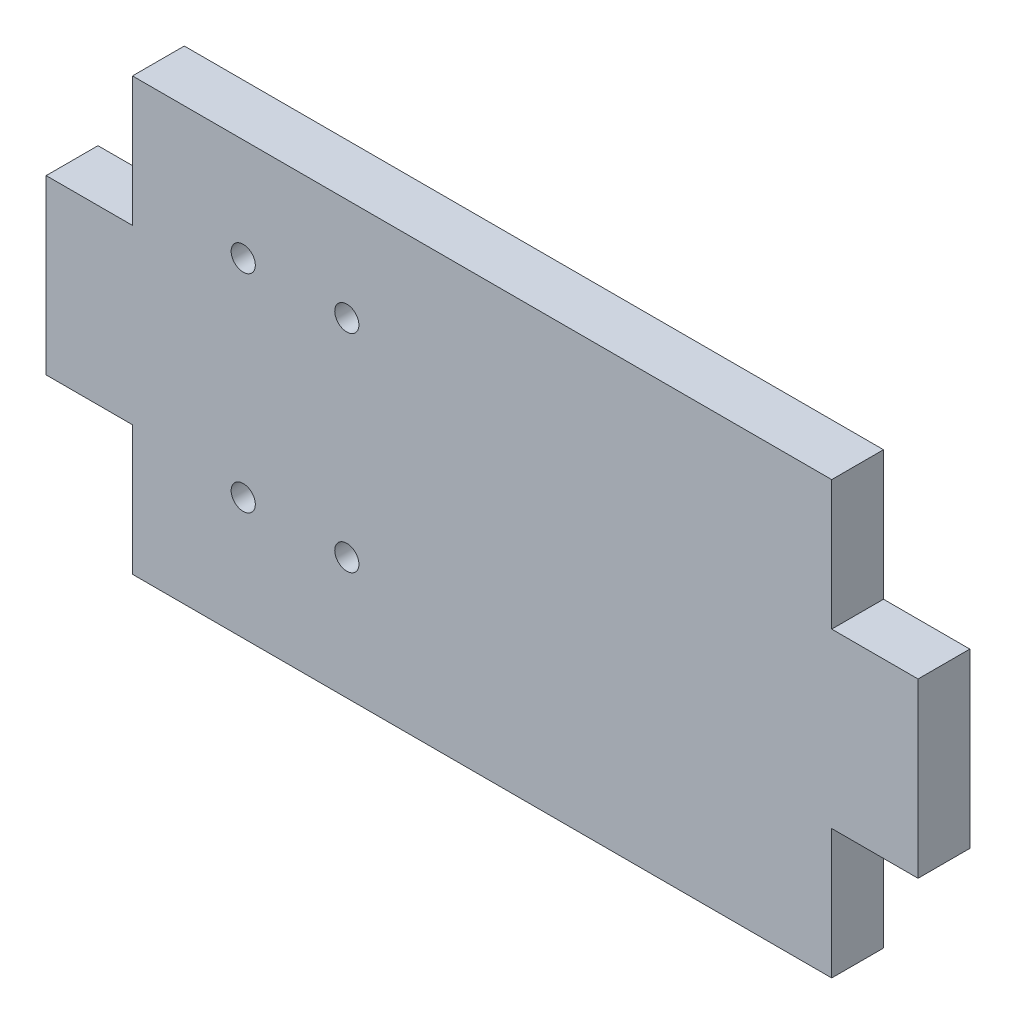
SolidWorks part; units mm, degrees
ref_plane "Plan de face" through (0, 0, 0) normal (0, 0, 1) x (1, 0, 0)
ref_plane "Plan de dessus" through (0, 0, 0) normal (0, 1, 0) x (1, 0, 0)
ref_plane "Plan de droite" through (0, 0, 0) normal (1, 0, 0) x (0, 0, -1)
sketch "Esquisse1" plane through (0, 0, 0) normal (0, 0, 1) x (1, 0, 0)
  line L1 (0, 0) -> (81, 0)
  line L2 (0, 0) -> (0, 50)
  line L3 (0, 50) -> (81, 50)
  line L4 (81, 0) -> (81, 50)
  line L5 (0, 35) -> (-10, 35)
  line L6 (0, 35) -> (0, 15)
  line L7 (0, 15) -> (-10, 15)
  line L8 (-10, 35) -> (-10, 15)
  line L9 (81, 35) -> (91, 35)
  line L10 (81, 35) -> (81, 15)
  line L11 (81, 15) -> (91, 15)
  line L12 (91, 35) -> (91, 15)
  point P13 (-10, 25)
  point P14 (0, 25)
  point P15 (91, 25)
  point P16 (81, 25)
  dimension "D1" = 81
  dimension "D2" = 50
  dimension "D3" = 10
  dimension "D4" = 20
  dimension "D5" = 10
  dimension "D6" = 20
extrude "Boss.-Extru.1" add sketch "Esquisse1" along normal blind 6 contours L5 L8 L7 L2 | L1 L4 L3 L2 | L12 L9 L4 L11 region at (40.5, 25, 0) region at (-5, 25, 0) region at (86, 25, 0)
sketch "Esquisse2" plane through (0, 0, 0) normal (0, 0, -1) x (-1, 0, 0)
  line L0 (-24.8289, 38.1224) -> (-12.8289, 38.1224) construction
  line L1 (-12.8289, 38.1224) -> (-12.8289, 14.1224) construction
  line L2 (-12.8289, 14.1224) -> (-24.8289, 14.1224) construction
  line L3 (-24.8289, 14.1224) -> (-24.8289, 38.1224) construction
  line L4 (0, 50) -> (-81, 50) construction
  line L5 (0, 14.85) -> (0, 35.15) construction
  circle A0 centre (-12.8289, 14.1224) radius 1.4
  circle A1 centre (-12.8289, 38.1224) radius 1.4
  circle A2 centre (-24.8289, 38.1224) radius 1.4
  circle A3 centre (-24.8289, 14.1224) radius 1.4
  dimension "D1" = 11.8776
  dimension "D2" = 24
  dimension "D3" = 2.8
  dimension "D4" = 12.8289
  dimension "D6" = 12
extrude "Enlèv. mat.-Extru.1" cut sketch "Esquisse2" against normal up to surface (6 mm away) up to face at (40.5, 25, 6)
sketch "Esquisse3" plane through (0, 0, 0) normal (0, 0, -1) x (-1, 0, 0)
  circle A0 centre (-24.8289, 38.1224) radius 3
  circle A1 centre (-12.8289, 38.1224) radius 3
  circle A2 centre (-12.8289, 14.1224) radius 3
  circle A3 centre (-24.8289, 14.1224) radius 3
  dimension "D1" = 6
extrude "Enlèv. mat.-Extru.2" cut sketch "Esquisse3" against normal blind 4
